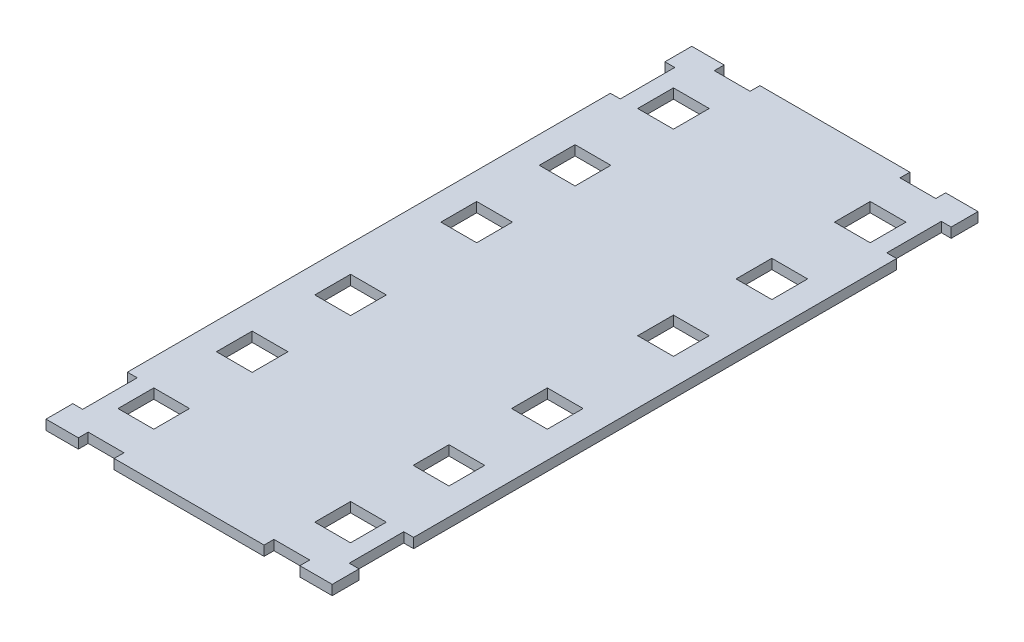
SolidWorks part; units mm, degrees
ref_plane "Alzado" through (0, 0, 0) normal (0, 0, 1) x (1, 0, 0)
ref_plane "Planta" through (0, 0, 0) normal (0, 1, 0) x (1, 0, 0)
ref_plane "Vista lateral" through (0, 0, 0) normal (1, 0, 0) x (0, 0, -1)
sketch "Croquis2" plane through (0, 0, 0) normal (0, 1, 0) x (1, 0, 0)
  line L0 (0, 140.5) -> (0, 321) construction
  line L1 (61.9143, 321) -> (61.9143, 315.5)
  line L2 (0, 0) -> (80, 0)
  line L3 (0, 140.5) -> (0, 321)
  line L4 (0, 321) -> (41.9143, 321)
  line L5 (80, 140.5) -> (80, 275.5)
  line L6 (61.9143, 315.5) -> (41.9143, 315.5)
  line L7 (41.9143, 315.5) -> (41.9143, 321)
  line L8 (61.9143, 321) -> (80, 321)
  line L9 (80, 306) -> (74.5, 306)
  line L10 (74.5, 306) -> (74.5, 275.5)
  line L11 (74.5, 275.5) -> (80, 275.5)
  line L12 (80, 306) -> (80, 321)
  line L13 (0, 140.5) -> (80, 140.5) construction
  line L14 (0, 140.5) -> (80, 140.5)
  dimension "D2" = 80
  dimension "D3" = 20
  dimension "D4" = 5.5
  dimension "D5" = 30.5
  dimension "D6" = 15
  dimension "D7" = 180.5
extrude "Saliente-Extruir1" add sketch "Croquis2" along normal blind 5.5 contours L3 L14 L5 L11 L10 L9 L12 L8 L1 L6 L7 L4 region at (39.4662, 0, -229.3597)
sketch "Croquis4" plane through (0, 0, 0) normal (0, 1, 0) x (1, 0, 0)
  line L0 (0, 285.75) -> (80, 285.75) construction
  line L1 (0, 140.5) -> (0, 321) construction
  line L2 (80, 306) -> (80, 321) construction
  line L3 (80, 321) -> (55, 321) construction
  line L6 (55, 321) -> (55, 140.5) construction
  line L7 (0, 140.5) -> (80, 140.5) construction
  line L9 (65, 275.75) -> (45, 275.75)
  line L10 (65, 275.75) -> (65, 295.75)
  line L11 (65, 295.75) -> (45, 295.75)
  line L12 (45, 275.75) -> (45, 295.75)
  line L13 (65, 275.75) -> (45, 295.75) construction
  line L14 (65, 295.75) -> (45, 275.75) construction
  line L15 (65, 220.75) -> (45, 220.75)
  line L16 (65, 220.75) -> (65, 240.75)
  line L17 (65, 240.75) -> (45, 240.75)
  line L18 (45, 220.75) -> (45, 240.75)
  line L19 (65, 220.75) -> (45, 240.75) construction
  line L20 (65, 240.75) -> (45, 220.75) construction
  line L21 (65, 165.75) -> (45, 165.75)
  line L22 (65, 165.75) -> (65, 185.75)
  line L23 (65, 185.75) -> (45, 185.75)
  line L24 (45, 165.75) -> (45, 185.75)
  line L25 (65, 165.75) -> (45, 185.75) construction
  line L26 (65, 185.75) -> (45, 165.75) construction
  point P12 (55, 285.75)
  point P18 (55, 230.75)
  point P23 (55, 175.75)
  dimension "D2" = 20
  dimension "D3" = 20
  dimension "D4" = 20
  dimension "D5" = 35
  dimension "D6" = 35
extrude "Cortar-Extruir3" cut sketch "Croquis4" along normal blind 10 contours L10 L9 L12 L11 | L16 L15 L18 L17 | L22 L21 L24 L23
mirror "Simetría3" about plane through (0, 5.5, 0) normal (-1, 0, 0) of bodies 105
mirror "Simetría4" about plane through (0, 5.5, -140.5) normal (0, 0, -1) of bodies 108
